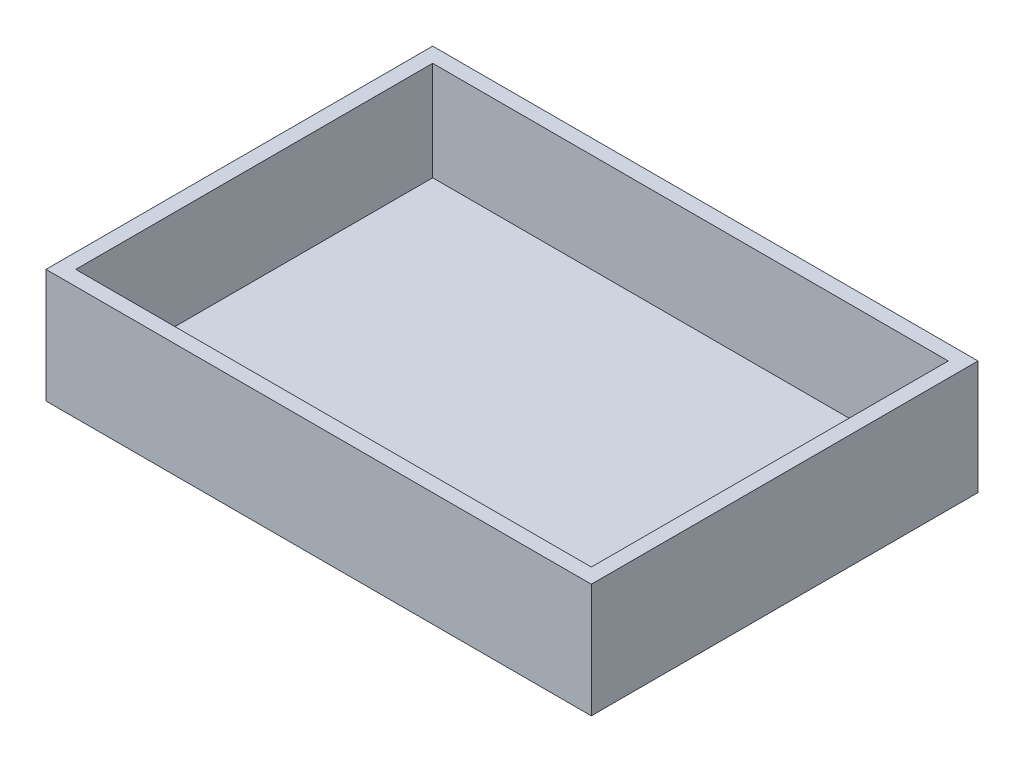
SolidWorks part; units mm, degrees
ref_plane "前视基准面" through (0, 0, 0) normal (0, 0, 1) x (1, 0, 0)
ref_plane "上视基准面" through (0, 0, 0) normal (0, 1, 0) x (1, 0, 0)
ref_plane "右视基准面" through (0, 0, 0) normal (1, 0, 0) x (0, 0, -1)
other "Configuration Table"
sketch "草图1" plane through (0, 0, 0) normal (0, 1, 0) x (1, 0, 0)
  line L1 (-27.5, 19.5) -> (27.5, 19.5)
  line L2 (-27.5, 19.5) -> (-27.5, -19.5)
  line L3 (-27.5, -19.5) -> (27.5, -19.5)
  line L4 (27.5, 19.5) -> (27.5, -19.5)
  line L5 (-27.5, 19.5) -> (27.5, -19.5) construction
  line L6 (-27.5, -19.5) -> (27.5, 19.5) construction
  point P0 (0, 0)
  dimension "D1" = 55
  dimension "D2" = 39
extrude "凸台-拉伸1" add sketch "草图1" along normal blind 11.5
shell "抽壳1" thickness 1.5 removed face at (0, 11.5, 0)
